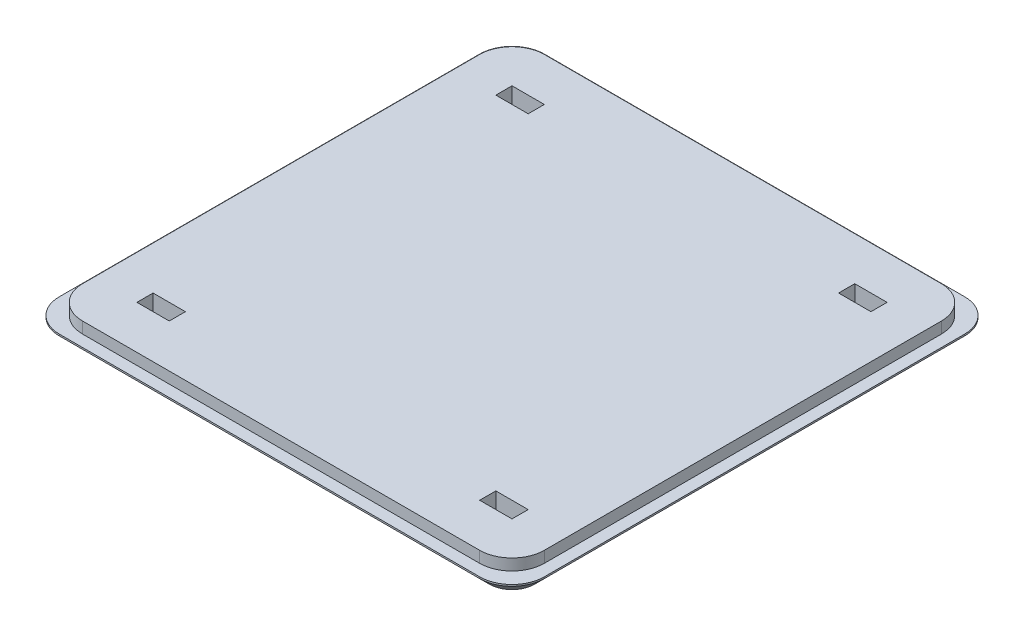
SolidWorks part; units mm, degrees
ref_plane "Front Plane" through (0, 0, 0) normal (0, 0, 1) x (1, 0, 0)
ref_plane "Top Plane" through (0, 0, 0) normal (0, 1, 0) x (1, 0, 0)
ref_plane "Right Plane" through (0, 0, 0) normal (1, 0, 0) x (0, 0, -1)
sketch "Sketch1" plane through (0, 0, 0) normal (0, 1, 0) x (1, 0, 0)
  line L1 (0, 0) -> (150, 0)
  line L2 (0, 0) -> (0, 150)
  line L3 (0, 150) -> (150, 150)
  line L4 (150, 0) -> (150, 150)
  dimension "D1" = 150
  dimension "D2" = 150
extrude "Boss-Extrude1" add sketch "Sketch1" along normal blind 3.5
sketch "Sketch2" plane through (0, 3.5, 0) normal (0, 1, 0) x (1, 0, 0)
  line L0 (150, 150) -> (0, 150) construction
  line L1 (3.6, 146.4) -> (146.4, 146.4)
  line L2 (3.6, 146.4) -> (3.6, 3.6)
  line L3 (3.6, 3.6) -> (146.4, 3.6)
  line L4 (146.4, 146.4) -> (146.4, 3.6)
  line L5 (0, 150) -> (0, 0) construction
  line L6 (150, 0) -> (150, 150) construction
  line L9 (0, 0) -> (150, 0) construction
  dimension "D1" = 3.6
  dimension "D2" = 3.6
  dimension "D3" = 3.6
  dimension "D4" = 3.6
extrude "Boss-Extrude2" add sketch "Sketch2" along normal blind 3.5
fillet "Fillet9" radius 10 2 edges at (146.4, 5.25, -3.6) (150, 1.75, 0)
fillet "Fillet10" radius 10 6 edges at (0, 1.75, -150) (3.6, 5.25, -146.4) (0, 1.75, 0) (3.6, 5.25, -3.6) (146.4, 5.25, -146.4) (150, 1.75, -150)
chamfer "Chamfer3" distance 3 angle 45 8 edges at (150, 0, -75) (147.0711, 0, -147.0711) (75, 0, -150) (2.9289, 0, -147.0711) (147.0711, 0, -2.9289) (0, 0, -75) (2.9289, 0, -2.9289) (75, 0, 0)
sketch "Sketch3" plane through (0, 7, 0) normal (0, 1, 0) x (1, 0, 0)
  line L0 (0, 140) -> (0, 10) construction
  line L1 (17, 22) -> (27, 22)
  line L2 (17, 22) -> (17, 17)
  line L3 (17, 17) -> (27, 17)
  line L4 (27, 22) -> (27, 17)
  line L5 (10, 0) -> (140, 0) construction
  point P4 (17, 19.5)
  dimension "D1" = 10
  dimension "D2" = 5
  dimension "D3" = 17
  dimension "D4" = 17
extrude "Cut-Extrude1" cut sketch "Sketch3" against normal blind 10
sketch "Sketch4" plane through (0, 7, 0) normal (0, 1, 0) x (1, 0, 0)
  line L0 (140, 150) -> (10, 150) construction
  line L1 (17, 128) -> (27, 128)
  line L2 (17, 128) -> (17, 133)
  line L3 (17, 133) -> (27, 133)
  line L4 (27, 128) -> (27, 133)
  line L5 (0, 140) -> (0, 10) construction
  dimension "D1" = 5
  dimension "D2" = 10
  dimension "D3" = 17
  dimension "D4" = 17
extrude "Cut-Extrude2" cut sketch "Sketch4" against normal blind 10
sketch "Sketch5" plane through (0, 7, 0) normal (0, 1, 0) x (1, 0, 0)
  line L0 (10, 0) -> (140, 0) construction
  line L1 (123, 17) -> (133, 17)
  line L2 (123, 17) -> (123, 22)
  line L3 (123, 22) -> (133, 22)
  line L4 (133, 17) -> (133, 22)
  line L5 (150, 10) -> (150, 140) construction
  dimension "D1" = 5
  dimension "D2" = 10
  dimension "D3" = 17
  dimension "D4" = 17
extrude "Cut-Extrude3" cut sketch "Sketch5" against normal blind 10
sketch "Sketch6" plane through (0, 7, 0) normal (0, 1, 0) x (1, 0, 0)
  line L0 (140, 150) -> (10, 150) construction
  line L1 (123, 128) -> (133, 128)
  line L2 (123, 128) -> (123, 133)
  line L3 (123, 133) -> (133, 133)
  line L4 (133, 128) -> (133, 133)
  line L5 (150, 10) -> (150, 140) construction
  dimension "D1" = 5
  dimension "D2" = 10
  dimension "D3" = 17
  dimension "D4" = 17
extrude "Cut-Extrude4" cut sketch "Sketch6" against normal blind 10
sketch "Sketch7" plane through (0, 0, 0) normal (0, -1, 0) x (1, 0, 0)
  line L1 (0, -140) -> (0, -10) construction
  line L2 (40, -52.5) -> (110, -52.5)
  line L3 (40, -52.5) -> (40, -97.5)
  line L4 (40, -97.5) -> (110, -97.5)
  line L5 (110, -52.5) -> (110, -97.5)
  line L6 (10, 0) -> (140, 0) construction
  dimension "D1" = 70
  dimension "D2" = 45
  dimension "D3" = 40
  dimension "D4" = 52.5
extrude "Boss-Extrude4" add sketch "Sketch7" along normal blind 30
fillet "Fillet12" radius 10 12 edges at (75, 0, -52.5) (75, 0, -97.5) (110, -15, -97.5) (110, -15, -52.5) (110, 0, -75) (40, -15, -52.5) (40, -15, -97.5) (40, 0, -75) (75, -30, -52.5) (110, -30, -75) (75, -30, -97.5) (40, -30, -75)
sketch "Sketch8" plane through (0, 0, -97.5) normal (0, 0, -1) x (-1, 0, 0)
  line L0 (-100, -10) -> (-100, 0) construction
  line L1 (-100, -5) -> (-50, -5)
  line L2 (-100, -5) -> (-100, -25)
  line L3 (-100, -25) -> (-50, -25)
  line L4 (-50, -5) -> (-50, -25)
  line L5 (-50, -20) -> (-50, -30) construction
  dimension "D1" = 20
  dimension "D2" = 50
extrude "Cut-Extrude5" cut sketch "Sketch8" against normal blind 501 contours L2 L1 L4 L3
fillet "Fillet15" radius 5 4 edges at (100, -5, -74.3301) (50, -5, -74.3301) (50, -25, -75) (100, -25, -75)
